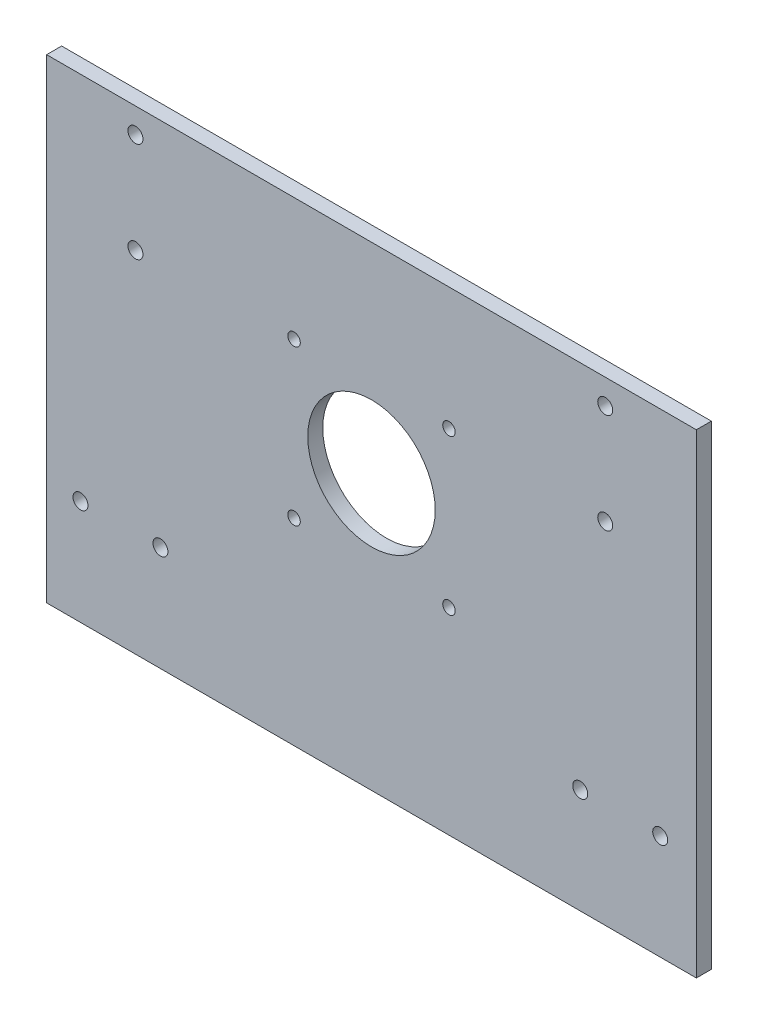
SolidWorks part; units mm, degrees
ref_plane "前视基准面" through (0, 0, 0) normal (0, 0, 1) x (1, 0, 0)
ref_plane "上视基准面" through (0, 0, 0) normal (0, 1, 0) x (1, 0, 0)
ref_plane "右视基准面" through (0, 0, 0) normal (1, 0, 0) x (0, 0, -1)
sketch "草图1" plane through (0, 0, 0) normal (0, 0, 1) x (1, 0, 0)
  line L1 (65, -47.5) -> (-65, -47.5)
  line L2 (65, -47.5) -> (65, 47.5)
  line L3 (65, 47.5) -> (-65, 47.5)
  line L4 (-65, -47.5) -> (-65, 47.5)
  line L5 (65, -47.5) -> (-65, 47.5) construction
  line L6 (65, 47.5) -> (-65, -47.5) construction
  point P0 (0, 0)
  dimension "D1" = 130
  dimension "D2" = 95
extrude "凸台-拉伸1" add sketch "草图1" along normal blind 3
sketch "草图2" plane through (0, 0, 3) normal (0, 0, 1) x (1, 0, 0)
  line L0 (0, -47.5) -> (0, -26.5) construction
  line L1 (-65, -47.5) -> (65, -47.5) construction
  line L2 (0, -26.5) -> (10, -26.5) construction
  circle A0 centre (10, -26.5) radius 1.5
  circle A1 centre (-10, -26.5) radius 1.5
  dimension "D3" = 3
  dimension "D1" = 21
  dimension "D2" = 10
sketch "草图3" plane through (0, 0, 0) normal (0, 0, -1) x (-1, 0, 0)
  circle A0 centre (-57.7671, -26.5) radius 1.5
  circle A1 centre (-41.7671, -26.5) radius 1.5
  circle A2 centre (42.2329, -26.5) radius 1.5
  circle A4 centre (58.2329, -26.5) radius 1.5
extrude "切除-拉伸2" cut sketch "草图3" against normal blind 10
sketch "草图4" plane through (0, 0, 0) normal (0, 0, -1) x (-1, 0, 0)
  circle A0 centre (-46.7671, 42.5) radius 1.5
  circle A1 centre (-46.7671, 22.5) radius 1.5
  circle A2 centre (47.2329, 42.5) radius 1.5
  circle A3 centre (47.2329, 22.5) radius 1.5
extrude "切除-拉伸3" cut sketch "草图4" against normal blind 10
sketch "草图15" plane through (0, 0, 0) normal (0, 0, -1) x (-1, 0, 0)
  circle A0 centre (0, 7.4526) radius 12.75
  dimension "D1" = 25.5
extrude "切除-拉伸8" cut sketch "草图15" against normal blind 10
sketch "草图16" plane through (0, 0, 0) normal (0, 0, -1) x (-1, 0, 0)
  line L1 (15.5, -8.0474) -> (-15.5, -8.0474) construction
  line L2 (15.5, -8.0474) -> (15.5, 22.9526) construction
  line L3 (15.5, 22.9526) -> (-15.5, 22.9526) construction
  line L4 (-15.5, -8.0474) -> (-15.5, 22.9526) construction
  line L5 (15.5, -8.0474) -> (-15.5, 22.9526) construction
  line L6 (15.5, 22.9526) -> (-15.5, -8.0474) construction
  circle A0 centre (-15.5, 22.9526) radius 1.25
  circle A1 centre (15.5, 22.9526) radius 1.25
  circle A2 centre (15.5, -8.0474) radius 1.25
  circle A3 centre (-15.5, -8.0474) radius 1.25
  point P0 (0, 7.4526)
  dimension "D3" = 2.5
  dimension "D4" = 2.5
  dimension "D5" = 2.5
  dimension "D6" = 2.5
  dimension "D1" = 31
  dimension "D2" = 31
extrude "切除-拉伸9" cut sketch "草图16" against normal blind 10
